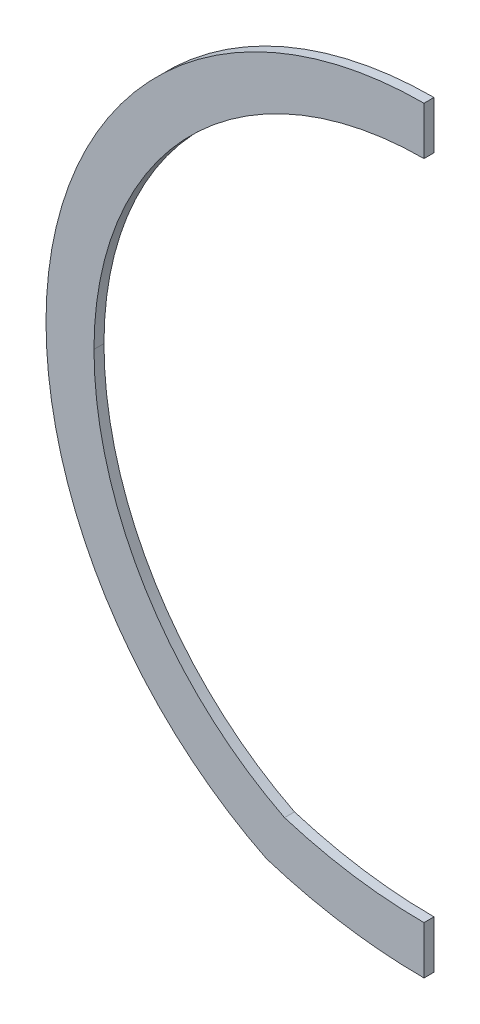
SolidWorks part; units mm, degrees
material "Balsa"
ref_plane "Front Plane" through (0, 0, 0) normal (0, 0, 1) x (1, 0, 0)
ref_plane "Top Plane" through (0, 0, 0) normal (0, 1, 0) x (1, 0, 0)
ref_plane "Right Plane" through (0, 0, 0) normal (1, 0, 0) x (0, 0, -1)
sketch "Sketch2" plane through (0, 0, 0) normal (0, 0, 1) x (1, 0, 0)
  line L0 (0, 0) -> (0.688, 245.4392) construction
  line L1 (-0.1309, -46.7153) -> (-0.2841, -101.3462) construction
  line L2 (0.0534, 19.05) -> (-169.3081, 19.05) construction
  line L3 (-72.7218, -93.726) -> (74.7111, -93.726) construction
  arc A1 (-120.0989, 19.05) -> (120.2036, 18.3433) centre (0.0534, 19.05) cw
  arc A2 (-120.0989, 19.05) -> (-50.0584, -93.726) centre (5.7147, 19.05) ccw
  arc A3 (-50.0584, -93.726) -> (50.1388, -93.726) centre (0.0402, 63.5) ccw
  arc A4 (120.2036, 18.3433) -> (50.1388, -93.726) centre (-5.6406, 19.0835) cw
  arc A5 (-104.8589, 19.05) -> (104.9639, 18.4329) centre (0.0534, 19.05) cw
  arc A6 (104.9639, 18.4329) -> (44.4049, -79.5534) centre (-5.6406, 19.0835) cw
  arc A7 (-44.324, -79.5535) -> (44.4049, -79.5534) centre (0.0402, 63.5) ccw
  arc A8 (-104.8589, 19.05) -> (-44.324, -79.5535) centre (5.7147, 19.05) ccw
  spline S0 degree 3 poles (-5521.0274, 5583.2546) (-1226.7801, 553.2855) (-196.9505, -260.8007) (69.4764, -82.4823) (75.8596, -77.7331) (81.7614, -72.3621) (85.2966, -68.8071) (85.996, -68.0862) (87.3792, -66.6243) (88.0639, -65.8824) (90.0847, -63.6371) (91.3894, -62.1126) (95.1787, -57.4581) (97.5389, -54.2471) (101.9343, -47.6137) (103.9694, -44.1914) (106.7765, -38.8981) (107.6712, -37.107) (109.3772, -33.4707) (110.1904, -31.6207) (112.481, -26.0415) (113.8153, -22.2742) (116.1105, -14.6467) (117.0712, -10.7866) (118.62, -2.9737) (119.208, 0.9791) (119.8028, 6.9796) (119.953, 8.9949) (120.1541, 13.0067) (120.2055, 15.0081) (120.2151, 20.9991) (119.8425, 28.9519) (118.7088, 36.835) (117.5685, 42.7208) (117.1399, 44.6783) (116.1841, 48.5842) (115.6559, 50.5346) (113.94, 56.3082) (112.6165, 60.0751) (109.6192, 67.4485) (107.9453, 71.055) (104.2453, 78.1066) (102.2192, 81.5518) (99.4588, 85.754) (98.8945, 86.5903) (97.7468, 88.2466) (97.1639, 89.0659) (95.3883, 91.4977) (94.1686, 93.0841) (90.4034, 97.7402) (87.752, 100.7072) (82.1689, 106.369) (79.2371, 109.0639) (74.6247, 112.8977) (73.0514, 114.1408) (70.6363, 115.9521) (69.821, 116.5478) (68.1799, 117.7153) (67.3537, 118.2875) (63.1947, 121.0918) (59.7778, 123.1535) (52.769, 126.9212) (49.1769, 128.6272) (41.816, 131.6806) (38.0473, 133.028) (33.2217, 134.4796) (32.2518, 134.758) (30.3116, 135.2882) (29.34, 135.5404) (26.4206, 136.2591) (24.4685, 136.6873) (18.5945, 137.8219) (14.6552, 138.3782) (6.7301, 139.0933) (2.7444, 139.252) (-2.2675, 139.1959) (-3.2714, 139.172) (-5.2821, 139.0983) (-6.2905, 139.0484) (-9.3072, 138.8606) (-11.3068, 138.6846) (-17.272, 138.0072) (-25.1357, 136.7069) (-32.823, 134.6274) (-38.5216, 132.7724) (-40.41, 132.1048) (-44.1641, 130.6694) (-46.0326, 129.9002) (-465.435, -55.3606) (264.7727, -2591.6725) (2155.1784, -7505.3224) knots -2.450405 -2.450405 -2.450405 -2.450405 0.03125 0.03125 0.0625 0.09375 0.09375 0.101563 0.101563 0.109375 0.109375 0.125 0.125 0.15625 0.15625 0.1875 0.1875 0.203125 0.203125 0.21875 0.21875 0.25 0.25 0.28125 0.28125 0.3125 0.3125 0.328125 0.328125 0.34375 0.34375 0.375 0.40625 0.40625 0.421875 0.421875 0.4375 0.4375 0.46875 0.46875 0.5 0.5 0.53125 0.53125 0.539063 0.539063 0.546875 0.546875 0.5625 0.5625 0.59375 0.59375 0.625 0.625 0.640625 0.640625 0.648438 0.648438 0.65625 0.65625 0.6875 0.6875 0.71875 0.71875 0.75 0.75 0.757813 0.757813 0.765625 0.765625 0.78125 0.78125 0.8125 0.8125 0.84375 0.84375 0.851563 0.851563 0.859375 0.859375 0.875 0.875 0.90625 0.9375 0.9375 0.953125 0.953125 0.96875 0.96875 4.508313 4.508313 4.508313 4.508313 only from (55.8537, -90.8749) to (-58.6671, 123.6507)
  spline S1 degree 3 poles (55.8537, -90.8749) (59.4151, -88.9779) (62.8499, -86.9173) (69.4764, -82.4823) (75.8596, -77.7331) (81.7614, -72.3621) (85.2966, -68.8071) (85.996, -68.0862) (87.3792, -66.6243) (88.0639, -65.8824) (90.0847, -63.6371) (91.3894, -62.1126) (95.1787, -57.4581) (97.5389, -54.2471) (101.9343, -47.6137) (103.9694, -44.1914) (106.7765, -38.8981) (107.6712, -37.107) (109.3772, -33.4707) (110.1904, -31.6207) (112.481, -26.0415) (113.8153, -22.2742) (116.1105, -14.6467) (117.0712, -10.7866) (118.62, -2.9737) (119.208, 0.9791) (119.8028, 6.9796) (119.953, 8.9949) (120.1541, 13.0067) (120.2055, 15.0081) (120.2151, 20.9991) (119.8425, 28.9519) (118.7088, 36.835) (117.5685, 42.7208) (117.1399, 44.6783) (116.1841, 48.5842) (115.6559, 50.5346) (113.94, 56.3082) (112.6165, 60.0751) (109.6192, 67.4485) (107.9453, 71.055) (104.2453, 78.1066) (102.2192, 81.5518) (99.4588, 85.754) (98.8945, 86.5903) (97.7468, 88.2466) (97.1639, 89.0659) (95.3883, 91.4977) (94.1686, 93.0841) (90.4034, 97.7402) (87.752, 100.7072) (82.1689, 106.369) (79.2371, 109.0639) (74.6247, 112.8977) (73.0514, 114.1408) (70.6363, 115.9521) (69.821, 116.5478) (68.1799, 117.7153) (67.3537, 118.2875) (63.1947, 121.0918) (59.7778, 123.1535) (52.769, 126.9212) (49.1769, 128.6272) (41.816, 131.6806) (38.0473, 133.028) (33.2217, 134.4796) (32.2518, 134.758) (30.3116, 135.2882) (29.34, 135.5404) (26.4206, 136.2591) (24.4685, 136.6873) (18.5945, 137.8219) (14.6552, 138.3782) (6.7301, 139.0933) (2.7444, 139.252) (-2.2675, 139.1959) (-3.2714, 139.172) (-5.2821, 139.0983) (-6.2905, 139.0484) (-9.3072, 138.8606) (-11.3068, 138.6846) (-17.272, 138.0072) (-25.1357, 136.7069) (-32.823, 134.6274) (-38.5216, 132.7724) (-40.41, 132.1048) (-44.1641, 130.6694) (-46.0326, 129.9002) (-51.5624, 127.4576) (-55.1595, 125.6458) (-58.6671, 123.6507) knots 0 0 0 0 0.03125 0.03125 0.0625 0.09375 0.09375 0.101563 0.101563 0.109375 0.109375 0.125 0.125 0.15625 0.15625 0.1875 0.1875 0.203125 0.203125 0.21875 0.21875 0.25 0.25 0.28125 0.28125 0.3125 0.3125 0.328125 0.328125 0.34375 0.34375 0.375 0.40625 0.40625 0.421875 0.421875 0.4375 0.4375 0.46875 0.46875 0.5 0.5 0.53125 0.53125 0.539063 0.539063 0.546875 0.546875 0.5625 0.5625 0.59375 0.59375 0.625 0.625 0.640625 0.640625 0.648438 0.648438 0.65625 0.65625 0.6875 0.6875 0.71875 0.71875 0.75 0.75 0.757813 0.757813 0.765625 0.765625 0.78125 0.78125 0.8125 0.8125 0.84375 0.84375 0.851563 0.851563 0.859375 0.859375 0.875 0.875 0.90625 0.9375 0.9375 0.953125 0.953125 0.96875 0.96875 1 1 1 1 construction
  spline S2 degree 3 poles (5694.5744, -5369.3669) (1292.3799, -516.6509) (187.1926, 314.492) (-76.9523, 111.0297) (-81.0984, 107.3558) (-85.9766, 102.3921) (-86.9369, 101.3807) (-88.8267, 99.3202) (-89.7577, 98.2691) (-92.4915, 95.0728) (-94.2304, 92.8907) (-99.2026, 86.1952) (-102.1931, 81.5333) (-106.1993, 74.2476) (-107.4545, 71.77) (-109.2154, 67.9791) (-109.782, 66.7031) (-110.874, 64.1258) (-111.4002, 62.8224) (-113.9097, 56.2871) (-115.5417, 50.9767) (-118.0823, 40.1978) (-118.9908, 34.7292) (-119.6657, 27.7928) (-119.7775, 26.4005) (-119.9543, 23.6055) (-120.0192, 22.2016) (-120.1418, 18.0057) (-120.1286, 15.2199) (-119.8102, 6.8959) (-119.2278, 1.3912) (-117.8014, -6.7994) (-117.2335, -9.5184) (-116.2404, -13.58) (-115.8858, -14.9311) (-115.1288, -17.6274) (-114.7258, -18.9739) (-112.6063, -25.6411) (-108.5276, -35.9696) (-103.1136, -45.6397) (-99.3011, -51.4722) (-98.5171, -52.628) (-96.9053, -54.9182) (-96.0765, -56.0537) (-93.5433, -59.4015) (-91.7865, -61.5635) (-86.3167, -67.8444) (-82.4051, -71.759) (-76.1398, -77.2217) (-73.9848, -78.9742) (-70.6503, -81.498) (-69.5218, -82.3217) (-67.2303, -83.9337) (-66.0665, -84.7222) (540.7318, -480.5341) (3882.3497, 5108.7967) (222.2795, -4616.5222) knots -3.63779 -3.63779 -3.63779 -3.63779 0.0625 0.0625 0.125 0.125 0.140625 0.140625 0.15625 0.15625 0.1875 0.1875 0.25 0.25 0.28125 0.28125 0.296875 0.296875 0.3125 0.3125 0.375 0.375 0.4375 0.4375 0.453125 0.453125 0.46875 0.46875 0.5 0.5 0.5625 0.5625 0.59375 0.59375 0.609375 0.609375 0.625 0.625 0.6875 0.75 0.75 0.765625 0.765625 0.78125 0.78125 0.8125 0.8125 0.875 0.875 0.90625 0.90625 0.921875 0.921875 0.9375 0.9375 9.012836 9.012836 9.012836 9.012836 only from (-58.6671, 123.6507) to (-50.3455, -93.5936)
  spline S3 degree 3 poles (-4578.1193, 6360.5009) (1102.8247, -3189.0685) (1357.3206, -1629.0846) (-2110.3169, 7551.2134) knots -196.711406 -196.711406 -196.711406 -196.711406 209.883914 209.883914 209.883914 209.883914 only from (49.819, -93.8744) to (55.8537, -90.8749)
  spline S4 degree 3 poles (49.819, -93.8744) (51.8584, -92.9316) (53.87, -91.9317) (55.8537, -90.8749) knots 0 0 0 0 1 1 1 1 construction
  spline S5 degree 3 poles (-58.6671, 123.6507) (-63.5487, 120.874) (-68.1774, 117.7887) (-76.9523, 111.0297) (-81.0984, 107.3558) (-85.9766, 102.3921) (-86.9369, 101.3807) (-88.8267, 99.3202) (-89.7577, 98.2691) (-92.4915, 95.0728) (-94.2304, 92.8907) (-99.2026, 86.1952) (-102.1931, 81.5333) (-106.1993, 74.2476) (-107.4545, 71.77) (-109.2154, 67.9791) (-109.782, 66.7031) (-110.874, 64.1258) (-111.4002, 62.8224) (-113.9097, 56.2871) (-115.5417, 50.9767) (-118.0823, 40.1978) (-118.9908, 34.7292) (-119.6657, 27.7928) (-119.7775, 26.4005) (-119.9543, 23.6055) (-120.0192, 22.2016) (-120.1418, 18.0057) (-120.1286, 15.2199) (-119.8102, 6.8959) (-119.2278, 1.3912) (-117.8014, -6.7994) (-117.2335, -9.5184) (-116.2404, -13.58) (-115.8858, -14.9311) (-115.1288, -17.6274) (-114.7258, -18.9739) (-112.6063, -25.6411) (-108.5276, -35.9696) (-103.1136, -45.6397) (-99.3011, -51.4722) (-98.5171, -52.628) (-96.9053, -54.9182) (-96.0765, -56.0537) (-93.5433, -59.4015) (-91.7865, -61.5635) (-86.3167, -67.8444) (-82.4051, -71.759) (-76.1398, -77.2217) (-73.9848, -78.9742) (-70.6503, -81.498) (-69.5218, -82.3217) (-67.2303, -83.9337) (-66.0665, -84.7222) (-60.2073, -88.5441) (-55.3561, -91.2432) (-50.3455, -93.5936) knots 0 0 0 0 0.0625 0.0625 0.125 0.125 0.140625 0.140625 0.15625 0.15625 0.1875 0.1875 0.25 0.25 0.28125 0.28125 0.296875 0.296875 0.3125 0.3125 0.375 0.375 0.4375 0.4375 0.453125 0.453125 0.46875 0.46875 0.5 0.5 0.5625 0.5625 0.59375 0.59375 0.609375 0.609375 0.625 0.625 0.6875 0.75 0.75 0.765625 0.765625 0.78125 0.78125 0.8125 0.8125 0.875 0.875 0.90625 0.90625 0.921875 0.921875 0.9375 0.9375 1 1 1 1 construction
  spline S6 degree 3 poles (-1759.0643, 7695.5768) (129.301, 75.0658) (104.9025, -75.6984) (45.8458, -95.3665) (44.8322, -95.6594) (41.7708, -96.4587) (39.7032, -96.8873) (35.5384, -97.6293) (33.4392, -97.9405) (29.2422, -98.4783) (27.1412, -98.7049) (20.8322, -99.2882) (16.6185, -99.55) (8.1799, -99.8877) (3.9548, -99.9623) (-4.5058, -99.9387) (-8.734, -99.8405) (-17.1695, -99.4557) (-21.3793, -99.1705) (-27.6778, -98.553) (-29.7745, -98.3152) (-33.9608, -97.7556) (-36.0504, -97.4344) (-39.177, -96.8603) (-40.2191, -96.653) (-42.292, -96.1992) (-43.3225, -95.953) (-45.3676, -95.407) (-46.3821, -95.1076) (-105.8729, -74.9194) (-124.4058, 77.5041) (2082.3243, 7613.4914) knots -1.777254 -1.777254 -1.777254 -1.777254 0.03125 0.03125 0.0625 0.0625 0.125 0.125 0.1875 0.1875 0.25 0.25 0.375 0.375 0.5 0.5 0.625 0.625 0.75 0.75 0.8125 0.8125 0.875 0.875 0.90625 0.90625 0.9375 0.9375 0.96875 0.96875 2.792352 2.792352 2.792352 2.792352 only from (49.8185, -93.8746) to (-50.3451, -93.5938)
  spline S7 degree 3 poles (49.8185, -93.8746) (48.8452, -94.325) (47.8521, -94.6984) (45.8458, -95.3665) (44.8322, -95.6594) (41.7708, -96.4587) (39.7032, -96.8873) (35.5384, -97.6293) (33.4392, -97.9405) (29.2422, -98.4783) (27.1412, -98.7049) (20.8322, -99.2882) (16.6185, -99.55) (8.1799, -99.8877) (3.9548, -99.9623) (-4.5058, -99.9387) (-8.734, -99.8405) (-17.1695, -99.4557) (-21.3793, -99.1705) (-27.6778, -98.553) (-29.7745, -98.3152) (-33.9608, -97.7556) (-36.0504, -97.4344) (-39.177, -96.8603) (-40.2191, -96.653) (-42.292, -96.1992) (-43.3225, -95.953) (-45.3676, -95.407) (-46.3821, -95.1076) (-48.3867, -94.4274) (-49.3773, -94.0483) (-50.3451, -93.5938) knots 0 0 0 0 0.03125 0.03125 0.0625 0.0625 0.125 0.125 0.1875 0.1875 0.25 0.25 0.375 0.375 0.5 0.5 0.625 0.625 0.75 0.75 0.8125 0.8125 0.875 0.875 0.90625 0.90625 0.9375 0.9375 0.96875 0.96875 1 1 1 1 construction
  spline S8 degree 1 poles (44.4895, -82.3468) (49.8828, -79.6661) knots 0 0 1 1 construction
  spline S9 degree 1 poles (49.8828, -79.6661) (-52.388, 112.6115) knots 0 0 1 1 construction
  spline S10 degree 1 poles (-52.388, 112.6115) (-44.952, -82.0958) knots 0 0 1 1 construction
  spline S11 degree 3 poles (44.4895, -82.3468) (44.9451, -82.1361) (45.8533, -81.7084) (47.2062, -81.0479) (48.5497, -80.3682) (49.4396, -79.9022) (49.8828, -79.6661) knots 0 0 0 0 0.250007 0.500014 0.750021 1.000028 1.000028 1.000028 1.000028 construction
  spline S12 degree 3 poles (49.8828, -79.6661) (51.4682, -78.8216) (54.6039, -77.0481) (60.6329, -73.2256) (67.7713, -67.9145) (75.6946, -60.7068) (85.376, -49.946) (92.2499, -39.5527) (97.0635, -29.9209) (99.9774, -23.2906) (102.9687, -14.8438) (105.5551, -4.452) (106.8747, 4.4138) (107.4138, 11.642) (107.598, 18.8242) (107.1791, 27.7507) (105.6575, 38.3493) (103.0737, 48.9109) (99.5091, 59.0529) (95.0071, 68.7524) (90.4672, 76.4728) (86.3465, 82.4205) (79.7918, 90.9419) (71.0678, 99.805) (59.5047, 108.4813) (50.3361, 114.0108) (40.7123, 118.5824) (32.2831, 121.5955) (25.3334, 123.4944) (18.366, 125.0225) (9.571, 126.2643) (-1.0997, 126.6912) (-11.9104, 126.0185) (-22.4327, 124.2743) (-36.1547, 120.5693) (-46.1487, 116.1604) (-52.388, 112.6115) knots 0 0 0 0 0.015625 0.03125 0.0625 0.09375 0.125 0.1875 0.203125 0.21875 0.25 0.28125 0.3125 0.328125 0.34375 0.375 0.40625 0.4375 0.46875 0.5 0.53125 0.546875 0.5625 0.625 0.65625 0.6875 0.71875 0.75 0.765625 0.78125 0.8125 0.84375 0.875 0.90625 0.9375 1 1 1 1 construction
  spline S13 degree 3 poles (-52.388, 112.6115) (-54.5585, 111.3769) (-58.8261, 108.7475) (-66.8816, 102.9693) (-76.1597, 94.757) (-85.9932, 83.258) (-92.681, 72.8203) (-97.1816, 63.9424) (-101.112, 54.6656) (-104.776, 42.7383) (-106.8137, 30.488) (-107.4512, 20.4245) (-107.4028, 10.4189) (-106.3564, 0.5368) (-104.3212, -9.2152) (-101.5955, -18.9231) (-97.0158, -30.5128) (-90.9605, -41.334) (-85.1677, -49.567) (-78.8706, -57.3154) (-71.8665, -64.3232) (-64.1621, -70.5906) (-57.9948, -74.9291) (-51.5954, -78.7902) (-47.193, -81.0446) (-44.952, -82.0958) knots 0 0 0 0 0.03125 0.0625 0.125 0.1875 0.25 0.28125 0.3125 0.375 0.4375 0.46875 0.5 0.5625 0.59375 0.625 0.6875 0.75 0.78125 0.8125 0.875 0.90625 0.9375 0.96875 1 1 1 1 construction
  spline S14 degree 1 poles (44.4849, -82.3489) (-44.9469, -82.0982) knots 0 0 1 1 construction
  spline S15 degree 3 poles (44.4849, -82.3489) (44.3746, -82.3999) (44.1627, -82.4934) (43.6492, -82.7012) (42.8561, -82.9839) (41.7841, -83.3184) (40.2245, -83.7477) (38.1103, -84.2445) (35.4106, -84.7656) (32.6063, -85.224) (28.7759, -85.7537) (23.885, -86.2821) (17.9201, -86.7432) (11.8971, -87.0512) (5.8396, -87.2261) (-2.2666, -87.2864) (-10.3738, -87.0974) (-18.3985, -86.6419) (-24.3556, -86.1481) (-29.2377, -85.5934) (-33.056, -85.0443) (-35.8555, -84.5718) (-38.5671, -84.0318) (-40.6899, -83.5223) (-42.2517, -83.0828) (-43.3238, -82.7417) (-44.1147, -82.4546) (-44.6269, -82.2439) (-44.8373, -82.1497) (-44.9469, -82.0982) knots 0 0 0 0 0.007812 0.015625 0.03125 0.046875 0.0625 0.09375 0.125 0.15625 0.1875 0.25 0.3125 0.375 0.4375 0.5 0.625 0.6875 0.75 0.8125 0.84375 0.875 0.90625 0.9375 0.953125 0.96875 0.984375 0.992188 1 1 1 1 construction
  point P12 (-0.2802, -99.9505)
  dimension "D3" = 19.05
  dimension "D4" = 93.726
  dimension "D5" = 63.5
  dimension "D6" = 15.24
  dimension "D1" = 12.7
  dimension "D2" = 12.7
extrude "Boss-Extrude1" add sketch "Sketch2" along normal mid plane 3.175
sketch "Sketch3" plane through (0, 0, 0) normal (1, 0, 0) x (0, 0, -1)
  line L1 (-100.0568, 212.3798) -> (108.5889, 212.3798)
  line L2 (-100.0568, 212.3798) -> (-100.0568, -170.6472)
  line L3 (-100.0568, -170.6472) -> (108.5889, -170.6472)
  line L4 (108.5889, 212.3798) -> (108.5889, -170.6472)
extrude "Cut-Extrude1" cut sketch "Sketch3" along normal through all
